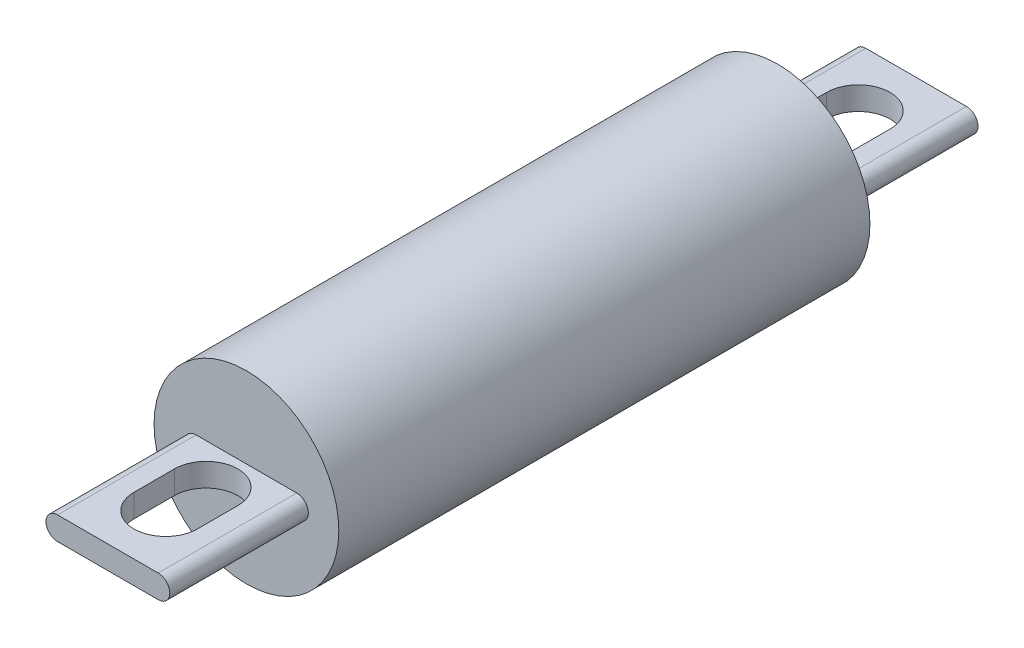
SolidWorks part; units mm, degrees
ref_plane "Front Plane" through (0, 0, 0) normal (0, 0, 1) x (1, 0, 0)
ref_plane "Top Plane" through (0, 0, 0) normal (0, 1, 0) x (1, 0, 0)
ref_plane "Right Plane" through (0, 0, 0) normal (1, 0, 0) x (0, 0, -1)
sketch "Sketch1" plane through (0, 0, 0) normal (0, 0, 1) x (1, 0, 0)
  circle A0 centre (0, 0) radius 12.7
  dimension "D1" = 25.4
extrude "Boss-Extrude1" add sketch "Sketch1" along normal mid plane 73.03
sketch "Sketch2" plane through (0, 0, 0) normal (0, 1, 0) x (1, 0, 0)
  line L0 (12.7, 36.515) -> (-12.7, 36.515) construction
  line L1 (-8.51, 36.515) -> (8.51, 36.515)
  line L2 (-8.51, 36.515) -> (-8.51, 55.565)
  line L3 (-8.51, 55.565) -> (8.51, 55.565)
  line L4 (8.51, 36.515) -> (8.51, 55.565)
  line L5 (-12.7, -36.515) -> (12.7, -36.515) construction
  line L6 (-8.51, -36.515) -> (8.51, -36.515)
  line L7 (-8.51, -36.515) -> (-8.51, -55.565)
  line L8 (-8.51, -55.565) -> (8.51, -55.565)
  line L9 (8.51, -36.515) -> (8.51, -55.565)
  line L10 (0, 42.06) -> (0, 47.62) construction
  line L11 (-4.365, 42.06) -> (-4.365, 47.62)
  line L12 (4.365, 42.06) -> (4.365, 47.62)
  line L13 (0, -42.06) -> (0, -47.62) construction
  line L14 (4.365, -42.06) -> (4.365, -47.62)
  line L15 (-4.365, -42.06) -> (-4.365, -47.62)
  line L16 (0, 37.695) -> (0, 36.515) construction
  line L17 (0, -37.695) -> (0, -36.515) construction
  arc A0 (-4.365, 42.06) -> (4.365, 42.06) centre (0, 42.06) ccw
  arc A1 (4.365, 47.62) -> (-4.365, 47.62) centre (0, 47.62) ccw
  arc A2 (4.365, -42.06) -> (-4.365, -42.06) centre (0, -42.06) ccw
  arc A3 (-4.365, -47.62) -> (4.365, -47.62) centre (0, -47.62) ccw
  point P12 (0, -36.515)
  point P14 (0, 36.515)
  point P17 (0, 44.84)
  point P22 (0, -44.84)
  dimension "D5" = 8.73
  dimension "D1" = 17.02
  dimension "D2" = 111.13
  dimension "D3" = 84.12
  dimension "D4" = 95.24
extrude "Boss-Extrude2" add sketch "Sketch2" along normal mid plane 3.18
fillet "Fillet1" 2 edges at (-8.51, 1.59, -46.04) (-8.51, -1.59, -46.04) type full round first side face at (0, 1.59, -46.04) second side face at (0, -1.59, -46.04) middle face at (-8.51, 0, -46.04)
fillet "Fillet2" 2 edges at (8.51, -1.59, -46.04) (8.51, 1.59, -46.04) type full round first side face at (0.795, -1.59, -46.04) second side face at (0.795, 1.59, -46.04) middle face at (8.51, 0, -46.04)
fillet "Fillet3" 2 edges at (8.51, 1.59, 46.04) (8.51, -1.59, 46.04) type full round first side face at (0, 1.59, 46.04) second side face at (0, -1.59, 46.04) middle face at (8.51, 0, 46.04)
fillet "Fillet4" 2 edges at (-8.51, 1.59, 46.04) (-8.51, -1.59, 46.04) type full round first side face at (-0.795, 1.59, 46.04) second side face at (-0.795, -1.59, 46.04) middle face at (-8.51, 0, 46.04)
